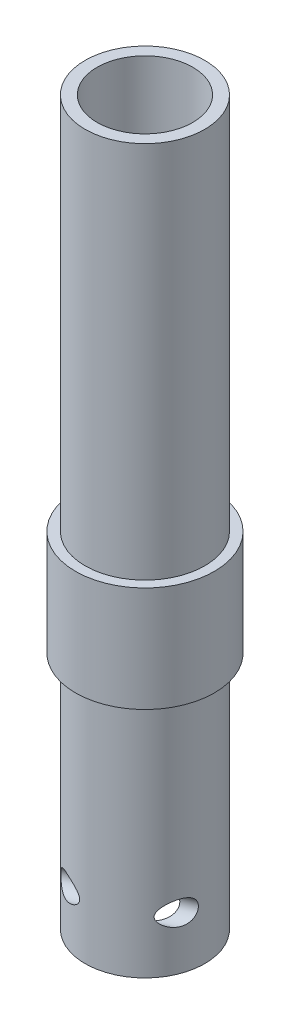
SolidWorks part; units mm, degrees
material "Polylactide (PLA)"
ref_plane "Front Plane" through (0, 0, 0) normal (0, 0, 1) x (1, 0, 0)
ref_plane "Top Plane" through (0, 0, 0) normal (0, 1, 0) x (1, 0, 0)
ref_plane "Right Plane" through (0, 0, 0) normal (1, 0, 0) x (0, 0, -1)
sketch "Sketch1" plane through (0, 0, 0) normal (0, 1, 0) x (1, 0, 0)
  circle A0 centre (0, 0) radius 12.5
  circle A1 centre (0, 0) radius 10
  dimension "D1" = 20
  dimension "D2" = 25
extrude "Boss-Extrude1" add sketch "Sketch1" along normal blind 100
sketch "Sketch6" plane through (0, 100, 0) normal (0, 1, 0) x (1, 0, 0)
  circle A0 centre (0, 0) radius 12.5
  circle A1 centre (0, 0) radius 10
  dimension "D1" = 20
  dimension "D2" = 25
extrude "Boss-Extrude2" add sketch "Sketch6" along normal blind 85 and the other way blind 4
sketch "Sketch7" plane through (0, 0, 0) normal (0, -1, 0) x (1, 0, 0)
  circle A0 centre (0, 0) radius 10
  circle A1 centre (0, 0) radius 14.5
  dimension "D1" = 20
  dimension "D2" = 29
extrude "Boss-Extrude3" add sketch "Sketch7" along normal blind 1 from offset 85 offset against normal yes
sketch "Sketch11" plane through (0, 0, 0) normal (1, 0, 0) x (0, 0, -1)
  line L1 (-17.505, -1.2) -> (17.505, -1.2)
  line L2 (-17.505, -1.2) -> (-17.505, 1.2)
  line L3 (-17.505, 1.2) -> (17.505, 1.2)
  line L4 (17.505, -1.2) -> (17.505, 1.2)
  line L5 (-17.505, -1.2) -> (17.505, 1.2) construction
  line L6 (-17.505, 1.2) -> (17.505, -1.2) construction
  point P0 (0, 0)
  dimension "D1" = 2.4
extrude "Cut-Extrude1" cut sketch "Sketch11" against normal through all both and the other way through all
sketch "Sketch13" plane through (0, 0, 0) normal (0, 0, 1) x (1, 0, 0)
  line L1 (-12.5, 1.2) -> (19.1091, 1.2)
  line L2 (-12.5, 1.2) -> (-12.5, 44)
  line L3 (-12.5, 44) -> (19.1091, 44)
  line L4 (19.1091, 1.2) -> (19.1091, 44)
  dimension "D1" = 42.8
extrude "Cut-Extrude3" cut sketch "Sketch13" against normal through all both and the other way through all
sketch "Sketch14" plane through (0, 85, 0) normal (0, 1, 0) x (1, 0, 0)
  circle A1 centre (0, 0) radius 14.5
  circle A2 centre (0, 0) radius 14.5
  dimension "D1" = 0
extrude "Boss-Extrude4" add sketch "Sketch14" along normal blind 21
sketch "Sketch15" plane through (0, 85, 0) normal (0, -1, 0) x (1, 0, 0)
  circle A0 centre (0, 0) radius 10
extrude "Cut-Extrude4" cut sketch "Sketch15" against normal blind 22
sketch "Sketch17" plane through (0, 44, 0) normal (0, -1, 0) x (1, 0, 0)
  circle A0 centre (0, 0) radius 10
  circle A1 centre (0, 0) radius 12.5
  circle A2 centre (0, 0) radius 12.5
  circle A3 centre (0, 0) radius 12.5
  circle M3 centre (0, 0) radius 10
  circle M4 centre (0, 0) radius 12.5
  dimension "D1" = 0
extrude "Boss-Extrude5" add sketch "Sketch17" along normal blind 10 contours M4 M3 region at (-12.1464, 44, 0)
sketch "Sketch18" plane through (35.019, 0, -14.7536) normal (0.9216, 0, -0.3883) x (-0.3883, 0, -0.9216)
  line L0 (-12.5, 84) -> (-12.5, 34) construction
  line L1 (-12.5, 34) -> (12.5, 34) construction
  circle A0 centre (-8.5, 45) radius 2.5
  dimension "D1" = 4
  dimension "D2" = 11
extrude "Cut-Extrude5" cut sketch "Sketch18" against normal blind 54
